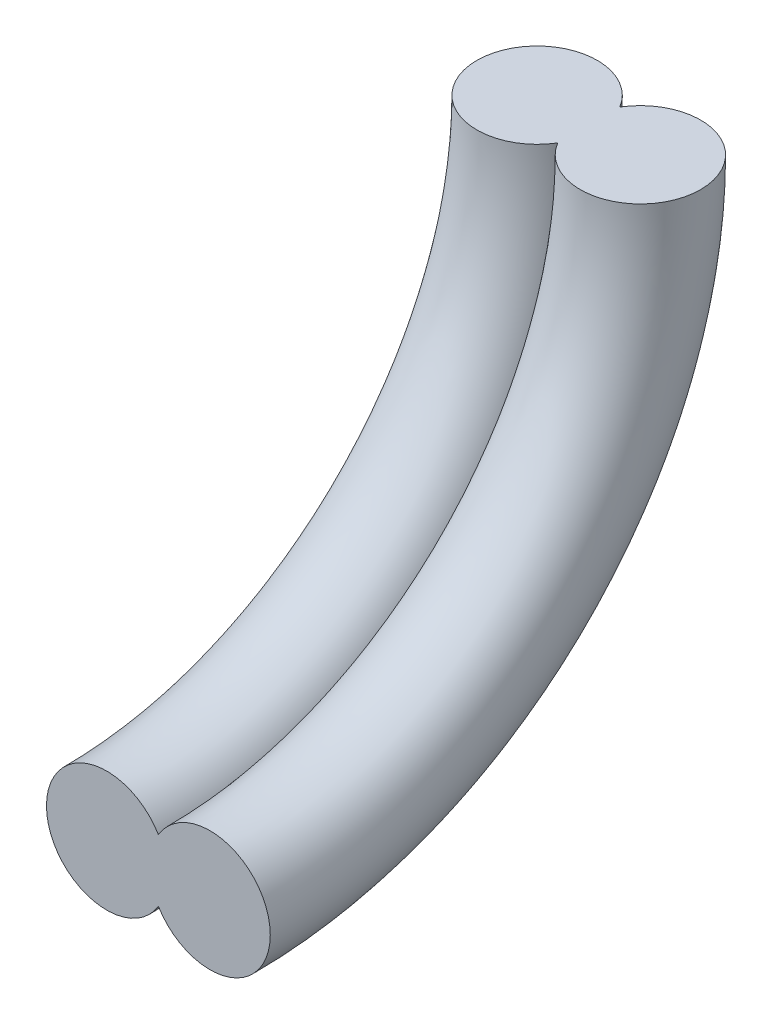
SolidWorks part; units mm, degrees
ref_plane "Front Plane" through (0, 0, 0) normal (0, 0, 1) x (1, 0, 0)
ref_plane "Top Plane" through (0, 0, 0) normal (0, 1, 0) x (1, 0, 0)
ref_plane "Right Plane" through (0, 0, 0) normal (1, 0, 0) x (0, 0, -1)
sketch "Sketch1" plane through (0, 0, 0) normal (0, 1, 0) x (1, 0, 0)
  line L0 (0, 0) -> (0, 0.6785) construction
  circle A0 centre (0.762, 0) radius 0.889
  dimension "D1" = 1.778
  dimension "D2" = 1.524
ref_plane "Plane1" through (0.2794, 0, 0) normal (1, 0, 0) x (0, 0, -1)
sketch "Sketch3" plane through (0.2794, 0, 0) normal (1, 0, 0) x (0, 0, -1)
  line L0 (0, 0) -> (0, 4.2593) construction
  arc A0 (0, 0) -> (-6.35, -6.35) centre (-6.35, 0) cw
  dimension "D1" = 6.35
  dimension "D2" = 6.35
sweep "Sweep2" add profiles "Sketch1" path "Sketch3"
mirror "Mirror4" about plane through (0, 0, 0) normal (1, 0, 0) of "Sweep2"
ref_axis "Axis1" through (0, 0.3315, 0) along (0, -1, 0)
equation "\"D2@Sketch3\"=\"D1@Sketch3\""
